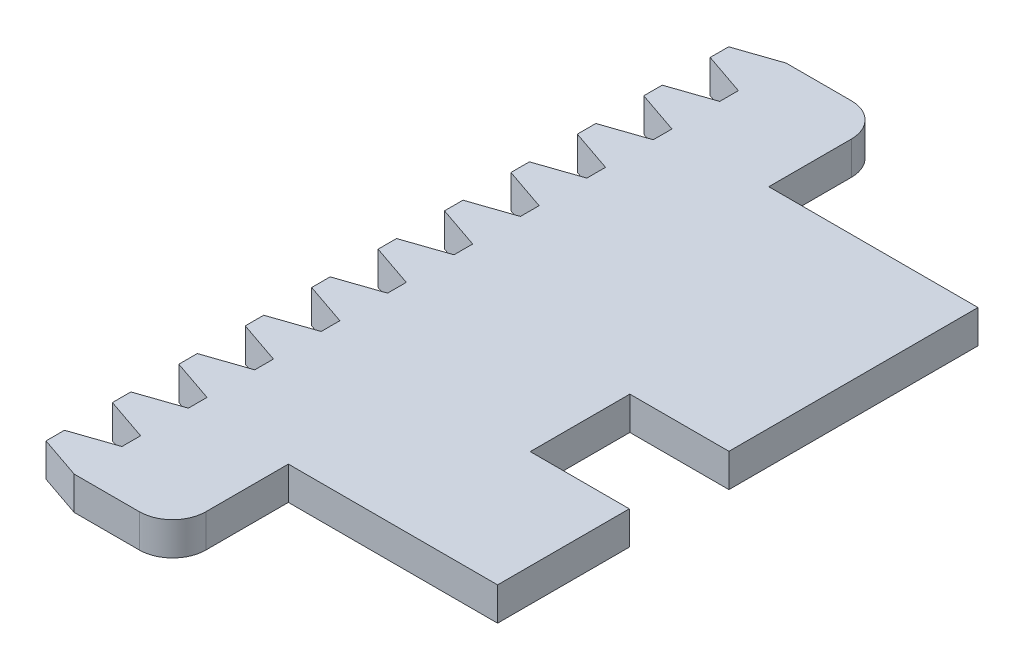
SolidWorks part; units mm, degrees
ref_plane "Front Plane" through (0, 0, 0) normal (0, 0, 1) x (1, 0, 0)
ref_plane "Top Plane" through (0, 0, 0) normal (0, 1, 0) x (1, 0, 0)
ref_plane "Right Plane" through (0, 0, 0) normal (1, 0, 0) x (0, 0, -1)
sketch "Sketch1" plane through (0, 0, 0) normal (0, 1, 0) x (1, 0, 0)
  line L4 (48.85, 21.7) -> (29.95, 21.7) construction
  line L5 (29.95, 29.157) -> (29.95, 21.7) construction
  line L6 (21.0585, 32.157) -> (26.95, 32.157) construction
  line L7 (21.0585, 32.157) -> (17.1887, 30.8335) construction
  line L8 (17.1887, 30.8335) -> (17.1887, 29.1665) construction
  line L13 (17.1887, 29.1665) -> (21.0585, 27.843) construction
  line L14 (21.0585, 26.157) -> (21.0585, 27.843) construction
  line L15 (21.0585, 26.157) -> (17.1887, 24.8335) construction
  line L16 (17.1887, 24.8335) -> (17.1887, 23.1665) construction
  line L17 (17.1887, 23.1665) -> (21.0585, 21.843) construction
  line L18 (21.0585, 20.157) -> (21.0585, 21.843) construction
  line L19 (21.0585, 20.157) -> (17.1887, 18.8335) construction
  line L20 (17.1887, 18.8335) -> (17.1887, 17.1665) construction
  line L21 (17.1887, 17.1665) -> (21.0585, 15.843) construction
  line L22 (21.0585, 14.157) -> (21.0585, 15.843) construction
  line L23 (21.0585, 14.157) -> (17.1887, 12.8335) construction
  line L24 (17.1887, 12.8335) -> (17.1887, 11.1665) construction
  line L25 (17.1887, 11.1665) -> (21.0585, 9.843) construction
  line L26 (21.0585, 8.157) -> (21.0585, 9.843) construction
  line L27 (21.0585, 8.157) -> (17.1887, 6.8335) construction
  line L28 (17.1887, 6.8335) -> (17.1887, 5.1665) construction
  line L29 (17.1887, 5.1665) -> (21.0585, 3.843) construction
  line L30 (21.0585, 2.157) -> (21.0585, 3.843) construction
  line L31 (21.0585, 2.157) -> (17.1887, 0.8335) construction
  line L32 (17.1887, 0.8335) -> (17.1887, -0.8335) construction
  line L33 (17.1887, -0.8335) -> (21.0585, -2.157) construction
  line L34 (21.0585, -3.843) -> (21.0585, -2.157) construction
  line L35 (21.0585, -3.843) -> (17.1887, -5.1665) construction
  line L36 (17.1887, -5.1665) -> (17.1887, -6.8335) construction
  line L37 (17.1887, -6.8335) -> (21.0585, -8.157) construction
  line L38 (21.0585, -9.843) -> (21.0585, -8.157) construction
  line L39 (21.0585, -9.843) -> (17.1887, -11.1665) construction
  line L40 (17.1887, -11.1665) -> (17.1887, -12.8335) construction
  line L41 (17.1887, -12.8335) -> (21.0585, -14.157) construction
  line L42 (21.0585, -15.843) -> (21.0585, -14.157) construction
  line L43 (21.0585, -15.843) -> (17.1887, -17.1665) construction
  line L44 (17.1887, -17.1665) -> (17.1887, -18.8335) construction
  line L45 (17.1887, -18.8335) -> (21.0585, -20.157) construction
  line L46 (21.0585, -21.843) -> (21.0585, -20.157) construction
  line L47 (21.0585, -21.843) -> (17.1887, -23.1665) construction
  line L48 (17.1887, -23.1665) -> (17.1887, -24.8335) construction
  line L49 (17.1887, -24.8335) -> (21.0585, -26.157) construction
  line L55 (21.0585, -27.843) -> (21.0585, -26.157) construction
  line L56 (21.0585, -27.843) -> (17.1887, -29.1665) construction
  line L57 (17.1887, -29.1665) -> (17.1887, -30.8335) construction
  line L99 (17.1887, -30.8335) -> (21.0585, -32.157) construction
  line L100 (26.95, -32.157) -> (21.0585, -32.157) construction
  line L105 (29.95, -21.7) -> (29.95, -29.157) construction
  line L107 (48.85, -21.7) -> (29.95, -21.7) construction
  line L108 (48.85, -9.8) -> (48.85, -21.7) construction
  line L109 (39.9, -9.8) -> (48.85, -9.8) construction
  line L110 (39.9, -0.8) -> (39.9, -9.8) construction
  line L111 (48.85, -0.8) -> (39.9, -0.8) construction
  line L112 (48.85, 21.7) -> (48.85, -0.8) construction
  line L113 (48.85, 21.7) -> (29.95, 21.7)
  line L114 (29.95, 29.157) -> (29.95, 21.7)
  line L115 (21.0585, 32.157) -> (26.95, 32.157)
  line L116 (21.0585, 32.157) -> (17.1887, 30.8335)
  line L117 (17.1887, 30.8335) -> (17.1887, 29.1665)
  line L118 (17.1887, 29.1665) -> (21.0585, 27.843)
  line L119 (21.0585, 26.157) -> (21.0585, 27.843)
  line L120 (21.0585, 26.157) -> (17.1887, 24.8335)
  line L121 (17.1887, 24.8335) -> (17.1887, 23.1665)
  line L122 (17.1887, 23.1665) -> (21.0585, 21.843)
  line L123 (21.0585, 20.157) -> (21.0585, 21.843)
  line L124 (21.0585, 20.157) -> (17.1887, 18.8335)
  line L125 (17.1887, 18.8335) -> (17.1887, 17.1665)
  line L126 (17.1887, 17.1665) -> (21.0585, 15.843)
  line L127 (21.0585, 14.157) -> (21.0585, 15.843)
  line L128 (21.0585, 14.157) -> (17.1887, 12.8335)
  line L129 (17.1887, 12.8335) -> (17.1887, 11.1665)
  line L130 (17.1887, 11.1665) -> (21.0585, 9.843)
  line L131 (21.0585, 8.157) -> (21.0585, 9.843)
  line L132 (21.0585, 8.157) -> (17.1887, 6.8335)
  line L133 (17.1887, 6.8335) -> (17.1887, 5.1665)
  line L134 (17.1887, 5.1665) -> (21.0585, 3.843)
  line L135 (21.0585, 2.157) -> (21.0585, 3.843)
  line L136 (21.0585, 2.157) -> (17.1887, 0.8335)
  line L137 (17.1887, 0.8335) -> (17.1887, -0.8335)
  line L138 (17.1887, -0.8335) -> (21.0585, -2.157)
  line L139 (21.0585, -3.843) -> (21.0585, -2.157)
  line L140 (21.0585, -3.843) -> (17.1887, -5.1665)
  line L141 (17.1887, -5.1665) -> (17.1887, -6.8335)
  line L142 (17.1887, -6.8335) -> (21.0585, -8.157)
  line L143 (21.0585, -9.843) -> (21.0585, -8.157)
  line L144 (21.0585, -9.843) -> (17.1887, -11.1665)
  line L145 (17.1887, -11.1665) -> (17.1887, -12.8335)
  line L146 (17.1887, -12.8335) -> (21.0585, -14.157)
  line L147 (21.0585, -15.843) -> (21.0585, -14.157)
  line L148 (21.0585, -15.843) -> (17.1887, -17.1665)
  line L149 (17.1887, -17.1665) -> (17.1887, -18.8335)
  line L150 (17.1887, -18.8335) -> (21.0585, -20.157)
  line L151 (21.0585, -21.843) -> (21.0585, -20.157)
  line L152 (21.0585, -21.843) -> (17.1887, -23.1665)
  line L153 (17.1887, -23.1665) -> (17.1887, -24.8335)
  line L154 (17.1887, -24.8335) -> (21.0585, -26.157)
  line L155 (21.0585, -27.843) -> (21.0585, -26.157)
  line L156 (21.0585, -27.843) -> (17.1887, -29.1665)
  line L157 (17.1887, -29.1665) -> (17.1887, -30.8335)
  line L160 (17.1887, -30.8335) -> (21.0585, -32.157)
  line L161 (26.95, -32.157) -> (21.0585, -32.157)
  line L162 (29.95, -21.7) -> (29.95, -29.157)
  line L163 (48.85, -21.7) -> (29.95, -21.7)
  line L164 (48.85, -9.8) -> (48.85, -21.7)
  line L165 (39.9, -9.8) -> (48.85, -9.8)
  line L166 (39.9, -0.8) -> (39.9, -9.8)
  line L167 (48.85, -0.8) -> (39.9, -0.8)
  line L168 (48.85, 21.7) -> (48.85, -0.8)
  line L169 (48.85, 28.7) -> (44.25, 28.7) construction
  line L170 (15.05, 32.157) -> (31.95, 32.157) construction
  line L171 (15.05, 32.157) -> (15.05, -32.157) construction
  line L172 (15.05, -32.157) -> (31.95, -32.157) construction
  line L173 (19.65, 32.157) -> (19.65, -32.157) construction
  line L174 (48.85, 28.7) -> (44.25, 28.7) construction
  line L175 (48.85, 28.7) -> (48.85, -28.7) construction
  line L176 (48.85, -28.7) -> (44.25, -28.7) construction
  line L177 (44.25, 28.7) -> (44.25, -28.7) construction
  line L178 (21.0585, 32.157) -> (15.05, 32.157) construction
  line L179 (15.05, -32.157) -> (21.0585, -32.157) construction
  line L180 (15.05, 32.157) -> (15.05, -32.157) construction
  line L181 (19.65, -32.157) -> (19.65, 32.157) construction
  line L182 (48.85, -28.7) -> (44.25, -28.7) construction
  line L183 (44.25, -28.7) -> (44.25, 28.7) construction
  line L184 (48.85, 28.7) -> (48.85, -28.7) construction
  line L185 (48.85, 0) -> (15.05, 0) construction
  line L186 (15.05, 0) -> (48.85, 0) construction
  line L187 (31.95, 32.157) -> (31.95, -32.157) construction
  line L188 (31.95, 32.157) -> (31.95, -32.157) construction
  line L189 (19.65, 21.7) -> (48.85, 21.7) construction
  line L190 (19.65, -21.7) -> (48.85, -21.7) construction
  line L191 (48.85, 21.7) -> (19.65, 21.7) construction
  line L192 (48.85, -3.8) -> (42.9, -3.8) construction
  line L193 (42.9, -3.8) -> (42.9, -6.8) construction
  line L194 (42.9, -6.8) -> (48.85, -6.8) construction
  line L195 (39.9, -5.3) -> (48.85, -5.3) construction
  line L196 (45.85, -0.8) -> (45.85, 18.7) construction
  line L197 (45.85, -9.8) -> (45.85, -18.7) construction
  line L198 (45.85, 18.7) -> (19.65, 18.7) construction
  line L199 (19.65, -18.7) -> (45.85, -18.7) construction
  line L200 (45.85, 18.7) -> (45.85, 21.7) construction
  line L201 (45.85, 18.7) -> (48.85, 18.7) construction
  line L202 (45.85, -18.7) -> (48.85, -18.7) construction
  line L203 (45.85, -18.7) -> (45.85, -21.7) construction
  line L204 (48.05, 28.7) -> (48.05, -28.7) construction
  line L205 (45.05, 28.7) -> (45.05, -28.7) construction
  line L206 (18.85, 32.157) -> (18.85, -32.157) construction
  line L207 (15.85, 32.157) -> (15.85, -32.157) construction
  line L208 (48.05, 28.7) -> (48.05, -0.8) construction
  line L209 (45.05, 28.7) -> (45.05, -0.8) construction
  line L210 (18.85, 32.157) -> (18.85, -32.157) construction
  line L211 (15.85, 32.157) -> (15.85, -32.157) construction
  line L212 (48.05, -9.8) -> (48.05, -28.7) construction
  line L213 (45.05, -9.8) -> (45.05, -28.7) construction
  arc A2 (29.95, 29.157) -> (26.95, 32.157) centre (26.95, 29.157) ccw construction
  arc A3 (26.95, -32.157) -> (29.95, -29.157) centre (26.95, -29.157) ccw construction
  arc A4 (29.95, 29.157) -> (26.95, 32.157) centre (26.95, 29.157) ccw
  arc A5 (26.95, -32.157) -> (29.95, -29.157) centre (26.95, -29.157) ccw
sketch "Sketch2" plane through (0, 0, 0) normal (0, 0, 1) x (1, 0, 0)
  line L1 (48.85, -3) -> (15.05, -3)
  line L2 (48.85, -3) -> (48.85, 0)
  line L3 (48.85, 0) -> (15.05, 0)
  line L4 (15.05, -3) -> (15.05, 0)
  line L5 (21, -3) -> (-21, -3) construction
extrude "Boss-Extrude1" add sketch "Sketch1" against normal up to vertex (3 mm away) up to point (15.05, -3, 0)
ref_plane "gear" through (0, 0, 3.8) normal (0, 0, 1) x (1, 0, 0)
ref_plane "front" through (0, 0, 21.7) normal (0, 0, 1) x (1, 0, 0)
ref_plane "back" through (0, 0, -21.7) normal (0, 0, 1) x (1, 0, 0)
ref_plane "top" through (48.05, 0, 0) normal (1, 0, 0) x (0, 0, -1)
ref_plane "bottom" through (15.85, 0, 0) normal (1, 0, 0) x (0, 0, -1)
